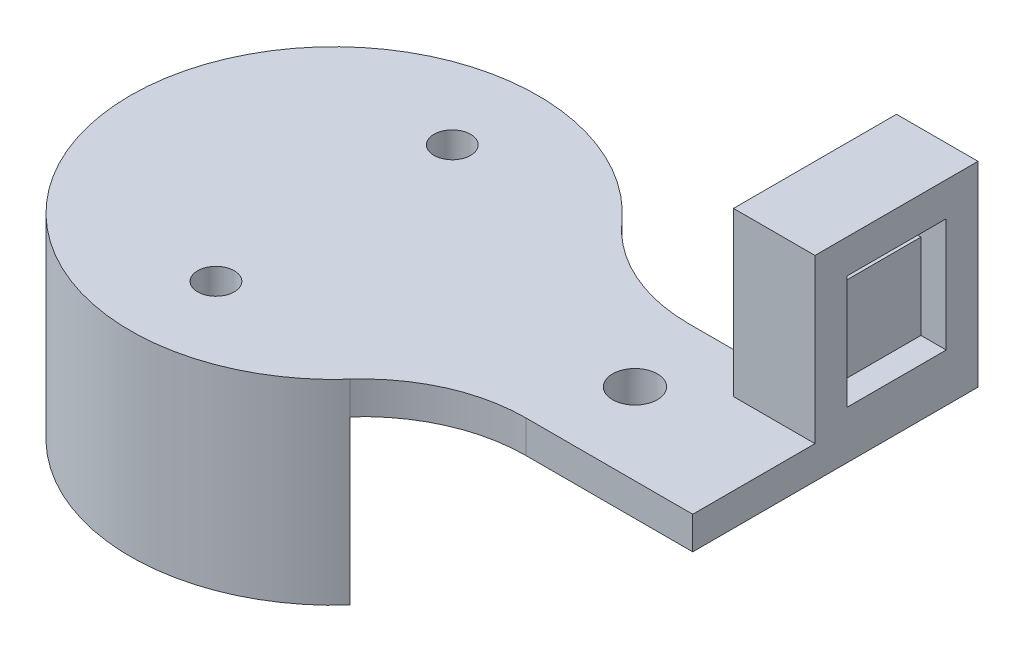
SolidWorks part; units mm, degrees
ref_plane "Front Plane" through (0, 0, 0) normal (0, 0, 1) x (1, 0, 0)
ref_plane "Top Plane" through (0, 0, 0) normal (0, 1, 0) x (1, 0, 0)
ref_plane "Right Plane" through (0, 0, 0) normal (1, 0, 0) x (0, 0, -1)
sketch "Sketch3" plane through (0, 0, 0) normal (0, 1, 0) x (1, 0, 0)
  line L0 (22.9129, 10) -> (44, 10)
  line L5 (54, 25) -> (54, -10)
  line L6 (44, 10) -> (44, 25)
  line L8 (54, -10) -> (22.9129, -10)
  line L10 (0, 0) -> (38.9129, 0) construction
  line L11 (44, 25) -> (54, 25)
  line L12 (44, 10) -> (44, -10) construction
  arc A5 (22.9129, 10) -> (22.9129, -10) centre (0, 0) ccw
  point P0 (0, 0)
  point P4 (44, 0)
  dimension "D1" = 50
  dimension "D2" = 54
  dimension "D3" = 10
  dimension "D4" = 15
  dimension "D5" = 20
extrude "Boss-Extrude1" add sketch "Sketch3" along normal blind 4
fillet "Fillet1" radius 20 2 edges at (22.9129, 2, 10) (22.9129, 2, -10)
sketch "Sketch1" plane through (103.3827, 0, 0) normal (0, 1, 0) x (1, 0, 0)
  line L6 (-103.3827, 14.5) -> (-103.3827, -14.5) construction
  line L16 (-21.097, 0) -> (-103.3827, 0) construction
  circle A7 centre (-103.3827, 14.5) radius 2.25
  circle A9 centre (-76.4698, 0) radius 2.25 construction
  circle A16 centre (-50.4698, 0) radius 2.25 construction
  circle A18 centre (-103.3827, -14.5) radius 2.25
  circle A19 centre (-66.4698, 0) radius 2.75
  point P5 (-103.3827, 0)
  dimension "D4" = 4.5
  dimension "D3" = 29
  dimension "D2" = 4.5
  dimension "D1" = 26.9129
  dimension "D5" = 5.5
  dimension "D6" = 10
  dimension "D7" = 26
extrude "Cut-Extrude3" cut sketch "Sketch1" along normal through all
sketch "Sketch5" plane through (0, 0, 0) normal (0, -1, 0) x (-1, 0, 0)
  line L1 (-23.9129, -10) -> (-71.2761, -10)
  line L2 (-23.9129, -10) -> (-23.9129, 10)
  line L3 (-23.9129, 10) -> (-71.2761, 10)
  line L4 (-71.2761, -10) -> (-71.2761, 10)
  point P4 (-23.9129, 0)
  dimension "D1" = 20
  dimension "D2" = 3
sketch "Sketch4" plane through (0, 0, 0) normal (0, -1, 0) x (1, 0, 0)
  line L0 (18.6339, 16.6667) -> (17.4523, 15.6098)
  line L1 (17.4523, -15.6098) -> (18.6339, -16.6667)
  arc A0 (18.6339, 16.6667) -> (18.6339, -16.6667) centre (0, 0) ccw
  arc A1 (18.6339, 16.6667) -> (18.6339, -16.6667) centre (0, 0) ccw construction
  arc A2 (14.7472, 15.6452) -> (14.7472, -15.6452) centre (0, 0) ccw
  arc A3 (14.7472, 15.6452) -> (17.4523, 15.6098) centre (16.119, 17.1005) ccw
  arc A4 (14.7472, -15.6452) -> (17.4523, -15.6098) centre (16.119, -17.1005) cw
  dimension "D3" = 3.5
  dimension "D4" = 2
extrude "Boss-Extrude2" add sketch "Sketch4" along normal blind 20 contours A2 A4 L1 A0 L0 A3
sketch "Sketch7" plane through (0, 4, 0) normal (0, 1, 0) x (1, 0, 0)
  line L0 (54, -10) -> (54, 25) construction
  line L1 (44, 25) -> (54, 25)
  line L2 (44, 25) -> (44, 5)
  line L3 (44, 5) -> (54, 5)
  line L4 (54, 25) -> (54, 5)
  line L5 (54, 25) -> (44, 25) construction
  dimension "D1" = 10
  dimension "D2" = 20
extrude "Boss-Extrude3" add sketch "Sketch7" along normal blind 20 contours L4 L3 L2 L1
sketch "Sketch8" plane through (54, 0, 0) normal (1, 0, 0) x (0, 0, -1)
  line L0 (25, 24) -> (25, 0) construction
  line L1 (8.9, 18.1) -> (21.1, 18.1)
  line L2 (8.9, 18.1) -> (8.9, 5.9)
  line L3 (8.9, 5.9) -> (21.1, 5.9)
  line L4 (21.1, 18.1) -> (21.1, 5.9)
  line L5 (21.1, 18.1) -> (8.9, 5.9) construction
  line L6 (25, 24) -> (5, 24) construction
  line L8 (8.9, 19.85) -> (21.1, 19.85)
  line L9 (8.9, 19.85) -> (8.9, 16.35)
  line L10 (8.9, 16.35) -> (21.1, 16.35)
  line L11 (21.1, 19.85) -> (21.1, 16.35)
  line L12 (8.9, 19.85) -> (21.1, 16.35) construction
  line L13 (8.9, 16.35) -> (21.1, 19.85) construction
  point P7 (15, 24)
  point P10 (25, 12)
  point P11 (15, 18.1)
  point P16 (15, 12)
  dimension "D1" = 12.2
  dimension "D2" = 3.5
extrude "Cut-Extrude4" cut sketch "Sketch8" against normal blind 3.1 contours L2 L3 L4 L1
extrude "Cut-Extrude5" cut sketch "Sketch8<3>" against normal up to next contours L8 L11 L10 L9
sketch "Sketch8<3>" plane through (54, 0, 0) normal (1, 0, 0) x (0, 0, -1) same geometry as "Sketch8"
